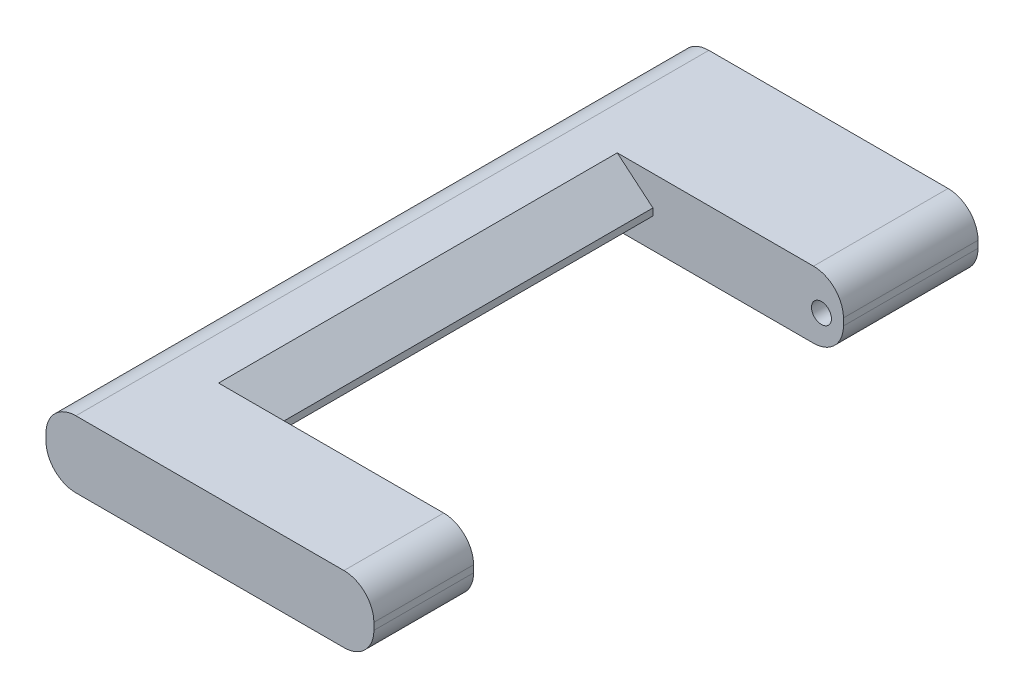
SolidWorks part; units mm, degrees
ref_plane "Alzado" through (0, 0, 0) normal (0, 0, 1) x (1, 0, 0)
ref_plane "Planta" through (0, 0, 0) normal (0, 1, 0) x (1, 0, 0)
ref_plane "Vista lateral" through (0, 0, 0) normal (1, 0, 0) x (0, 0, -1)
sketch "Croquis1" plane through (0, 0, 0) normal (0, 0, 1) x (1, 0, 0)
  line L0 (15.2964, 5.3464) -> (15.2964, -6.0536)
  line L1 (15.2964, 5.3464) -> (-50.4902, 5.3464)
  line L2 (15.2964, -6.0536) -> (-50.4902, -6.0536)
  line L3 (-50.4902, 5.3464) -> (-50.4902, -6.0536)
  arc A0 (16.15, 5.7) -> (15.65, 6.2) centre (15.65, 5.7) ccw construction
  arc A1 (15.65, -6.2) -> (16.15, -5.7) centre (15.65, -5.7) ccw construction
extrude "Saliente-Extruir1" add sketch "Croquis1" along normal blind 20 contours L2 L3 L1 L0
sketch "Croquis2" plane through (0, 0, 0) normal (0, 0, -1) x (-1, 0, 0)
  line L0 (50.4902, 5.3464) -> (50.4902, -6.0536)
  line L1 (50.4902, 5.3464) -> (28.7182, 5.3464)
  line L2 (50.4902, -6.0536) -> (28.7182, -6.0536)
  line L3 (28.7182, 5.3464) -> (28.7182, -6.0536)
extrude "Saliente-Extruir2" add sketch "Croquis2" along normal blind 100
sketch "Croquis3" plane through (0, 0, -100) normal (0, 0, -1) x (-1, 0, 0)
  line L0 (50.4902, 5.3464) -> (50.4902, -6.0536)
  line L1 (50.4902, 5.3464) -> (-9.5098, 5.3464)
  line L2 (50.4902, -6.0536) -> (-9.5098, -6.0536)
  line L3 (-9.5098, 5.3464) -> (-9.5098, -6.0536)
  dimension "D1" = 60
extrude "Saliente-Extruir3" add sketch "Croquis3" against normal blind 20 and the other way blind 7
sketch "Croquis4" plane through (0, 5.3464, 0) normal (0, 1, 0) x (1, 0, 0)
  line L8 (9.5098, 107) -> (-50.4902, 107)
  line L9 (-50.4902, 107) -> (-50.4902, -20)
  line L10 (-50.4902, -20) -> (15.2964, -20)
  line L11 (15.2964, -20) -> (15.2964, 0)
  line L12 (15.2964, 0) -> (-28.7182, 0)
  line L13 (-28.7182, 0) -> (-28.7182, 80)
  line L14 (-28.7182, 80) -> (9.5098, 80)
  line L15 (9.5098, 80) -> (9.5098, 107)
  line L16 (9.5098, 107) -> (-50.4902, 107)
  line L17 (-50.4902, 107) -> (-50.4902, -20)
  line L18 (-50.4902, -20) -> (15.2964, -20)
  line L19 (15.2964, -20) -> (15.2964, 0)
  line L20 (15.2964, 0) -> (-28.7182, 0)
  line L21 (-28.7182, 0) -> (-28.7182, 80)
  line L22 (-28.7182, 80) -> (9.5098, 80)
  line L23 (9.5098, 80) -> (9.5098, 107)
  dimension "D1" = 0
extrude "Saliente-Extruir4" add sketch "Croquis4" along normal blind 2
fillet "Redondeo1" radius 6 2 edges at (-50.4902, -6.0536, -43.5) (-50.4902, 7.3464, -43.5)
chamfer "Chaflán1" distance 6 angle 50 2 edges at (-28.7182, 7.3464, -40) (-28.7182, -6.0536, -40) first distance on face at (-28.7182, 0.6464, -40)
sketch "Croquis5" plane through (0, 0, -107) normal (0, 0, -1) x (-1, 0, 0)
  circle A0 centre (-5.1, 0) radius 2
  dimension "D1" = 4
extrude "Cortar-Extruir1" cut sketch "Croquis5" against normal up to next
fillet "Redondeo2" radius 6 4 edges at (15.2964, -6.0536, 10) (15.2964, 7.3464, 10) (9.5098, -6.0536, -93.5) (9.5098, 7.3464, -93.5)
